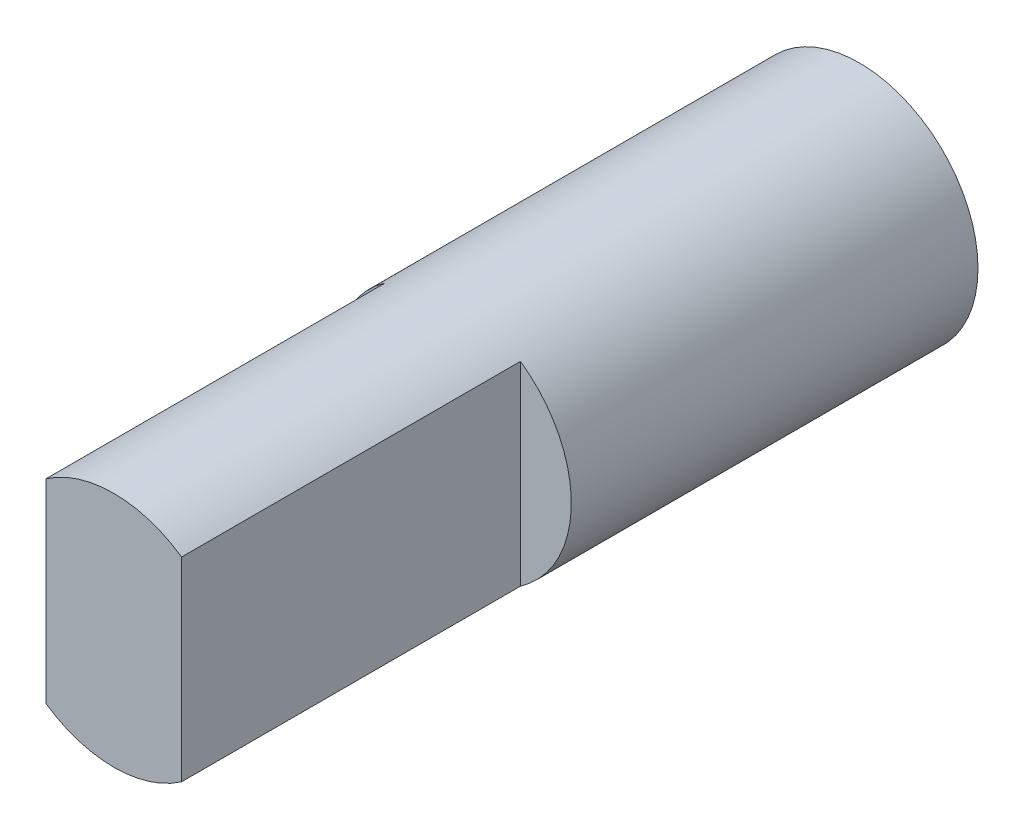
SolidWorks part; units mm, degrees
ref_plane "Alzado" through (0, 0, 0) normal (0, 0, 1) x (1, 0, 0)
ref_plane "Planta" through (0, 0, 0) normal (0, 1, 0) x (1, 0, 0)
ref_plane "Vista lateral" through (0, 0, 0) normal (1, 0, 0) x (0, 0, -1)
sketch "Croquis1" plane through (0, 0, 0) normal (0, 0, 1) x (1, 0, 0)
  circle A0 centre (0, 0) radius 1.75
  dimension "D1" = 3.5
extrude "Saliente-Extruir1" add sketch "Croquis1" along normal blind 11
sketch "Croquis2" plane through (0, 0, 0) normal (0, 1, 0) x (1, 0, 0)
  line L0 (0, 0) -> (0, -6) construction
  line L1 (0, -6) -> (1, -6) construction
  line L2 (1.75, -11) -> (1.75, 0) construction
  line L7 (-1, -6) -> (-1.75, -6)
  line L8 (-1, -6) -> (-1, -11)
  line L9 (-1, -11) -> (-1.75, -11)
  line L10 (-1.75, -6) -> (-1.75, -11)
  line L11 (1, -6) -> (1.75, -6)
  line L12 (1, -6) -> (1, -11)
  line L13 (1, -11) -> (1.75, -11)
  line L14 (1.75, -6) -> (1.75, -11)
  dimension "D1" = 6
  dimension "D2" = 1
extrude "Cortar-Extruir1" cut sketch "Croquis2" against normal blind 1.75 and the other way blind 1.75
